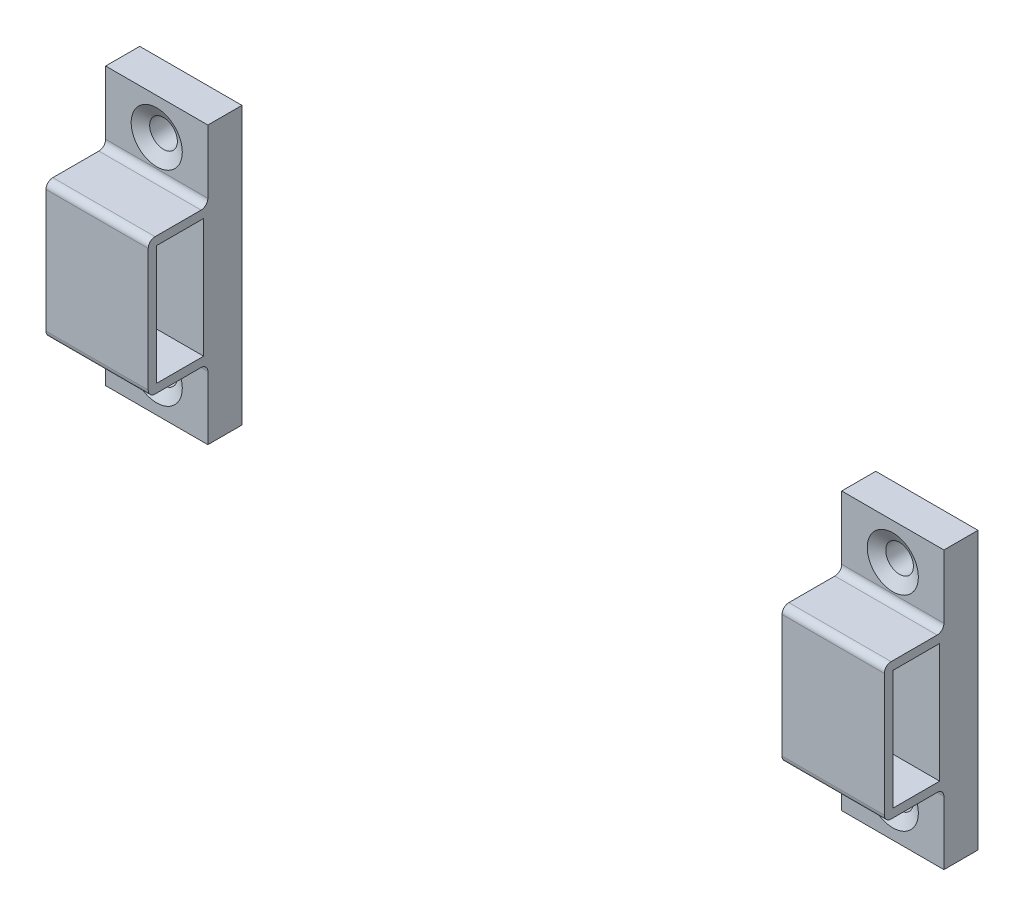
SolidWorks part; units mm, degrees
ref_plane "Front Plane" through (0, 0, 0) normal (0, 0, 1) x (1, 0, 0)
ref_plane "Top Plane" through (0, 0, 0) normal (0, 1, 0) x (1, 0, 0)
ref_plane "Right Plane" through (0, 0, 0) normal (1, 0, 0) x (0, 0, -1)
sketch "Sketch1" plane through (0, 0, 0) normal (0, 0, 1) x (1, 0, 0)
  line L0 (0, 25.7969) -> (0, -25.7969) construction
  line L1 (152.4, 0) -> (-152.4, 0) construction
  line L2 (9.525, 25.7969) -> (-9.525, 25.7969) construction
  line L3 (0, 19.05) -> (0, -19.05) construction
  line L4 (0, 9.525) -> (0, -9.525) construction
  line L5 (-152.4, 0) -> (-122.2375, 0) construction
  line L6 (152.4, 0) -> (127, 0) construction
  line L7 (152.4, 0) -> (-95.25, 0) construction
  line L8 (0, 12.7) -> (0, -12.7) construction
  line L9 (-4.1672, 0) -> (4.1672, 0) construction
  line L10 (0, 36.5125) -> (0, -36.5125) construction
sketch "Sketch3" plane through (0, 0, 0) normal (1, 0, 0) x (0, 0, -1)
  line L0 (3.175, 0) -> (-3.175, 0) construction
  line L1 (-9.525, 0) -> (9.525, 0) construction
  line L2 (-1.5875, 0) -> (1.5875, 0) construction
  line L3 (8.7312, 0) -> (-8.7312, 0) construction
sketch "Sketch4" plane through (0, 0, 0) normal (0, 0, 1) x (1, 0, 0)
  line L1 (-152.4, 9.525) -> (50.8, 9.525)
  line L2 (-152.4, 9.525) -> (-152.4, -9.525)
  line L3 (-152.4, -9.525) -> (50.8, -9.525)
  line L4 (50.8, 9.525) -> (50.8, -9.525)
  point P4 (152.4, 9.525)
  point P8 (-152.4, -9.525)
  dimension "D1" = 203.2
extrude "Boss-Extrude1" add sketch "Sketch4" along normal up to vertex (3.175 mm away) and the other way up to vertex (3.175 mm away) up to point (0, 0, 3.175) other way up to point (0, 0, -3.175)
chamfer "Chamfer1" distance 1.27 angle 45 4 edges at (50.8, -9.525, 0) (50.8, 0, -3.175) (50.8, 9.525, 0) (50.8, 0, 3.175)
sketch "Sketch5" plane through (0, 0, 3.175) normal (0, 0, 1) x (1, 0, 0)
  line L0 (-142.875, -7.9375) -> (-142.875, 0) construction
  line L5 (152.4, 0) -> (-152.4, 0) construction
  line L6 (-142.875, -7.9375) -> (-142.875, -9.525) construction
  line L7 (-152.4, -9.525) -> (49.53, -9.525) construction
  line L8 (-142.875, 0) -> (-142.875, 7.9375) construction
  line L9 (-142.875, 7.9375) -> (-142.875, 9.525) construction
  line L10 (49.53, 9.525) -> (-152.4, 9.525) construction
  line L12 (-152.4, -9.525) -> (-133.35, -9.525) construction
  line L13 (-152.4, -9.525) -> (-152.4, 9.525) construction
  line L14 (-152.4, 9.525) -> (-133.35, 9.525) construction
  line L15 (-133.35, -9.525) -> (-133.35, 9.525) construction
  line L16 (-152.4, -9.525) -> (-133.35, 9.525) construction
  line L17 (-152.4, 9.525) -> (-133.35, -9.525) construction
  line L18 (-152.4, 9.525) -> (-152.4, -9.525) construction
  line L19 (-95.25, 0) -> (-104.775, 0) construction
  line L20 (-142.875, 0) -> (-134.9375, 0) construction
  circle A0 centre (-142.875, 0) radius 7.9375
  dimension "D1" = 9.525
  dimension "D2" = 30.1625
extrude "Boss-Extrude2" add sketch "Sketch5" along normal blind 12.7
sketch "Sketch6" plane through (0, 0, 15.875) normal (0, 0, 1) x (1, 0, 0)
  line L0 (49.53, 9.525) -> (-152.4, 9.525) construction
  line L1 (-151.892, -9.525) -> (-133.858, -9.525)
  line L2 (-152.4, -9.017) -> (-152.4, 9.017)
  line L3 (-151.892, 9.525) -> (-133.858, 9.525)
  line L4 (-133.35, -9.017) -> (-133.35, 9.017)
  line L5 (-152.4, -9.525) -> (-133.35, 9.525) construction
  line L6 (-152.4, 9.525) -> (-133.35, -9.525) construction
  line L7 (-152.4, 9.525) -> (-152.4, -9.525) construction
  line L8 (-152.4, 9.017) -> (-151.892, 9.525)
  line L9 (-133.858, 9.525) -> (-133.35, 9.017)
  line L10 (-133.858, -9.525) -> (-133.35, -9.017)
  line L11 (-152.4, -9.017) -> (-151.892, -9.525)
  circle A0 centre (-142.875, 0) radius 7.9375 construction
  point P0 (-142.875, 0)
extrude "Boss-Extrude3" add sketch "Sketch6" along normal blind 3.175
chamfer "Chamfer2" distance 1.27 angle 45 4 edges at (-142.875, 9.525, 19.05) (-133.35, 0, 19.05) (-142.875, -9.525, 19.05) (-152.4, 0, 19.05)
fillet "Fillet1" radius 0.635 2 edges at (-134.9375, 0, 15.875) (-134.9375, 0, 3.175)
fillet "Fillet2" radius 0.254 8 edges at (-152.4, 0, 15.875) (-152.146, -9.271, 15.875) (-142.875, -9.525, 15.875) (-133.604, -9.271, 15.875) (-133.35, 0, 15.875) (-133.604, 9.271, 15.875) (-142.875, 9.525, 15.875) (-152.146, 9.271, 15.875)
ref_plane "Plane1" through (127, 0, 0) normal (1, 0, 0) x (0, 0, -1)
sketch "Sketch7" plane through (127, 0, 0) normal (1, 0, 0) x (0, 0, -1)
  line L0 (11.5094, 25.7969) -> (11.5094, -25.7969)
  line L1 (0, 0) -> (11.5094, 0) construction
  line L2 (11.5094, 25.7969) -> (5.1594, 25.7969)
  line L3 (5.1594, 25.7969) -> (5.1594, 12.7)
  line L4 (5.1594, 12.7) -> (-5.9531, 12.7)
  line L5 (-5.9531, 12.7) -> (-5.9531, -12.7)
  line L6 (-5.9531, -12.7) -> (5.1594, -12.7)
  line L7 (5.1594, -12.7) -> (5.1594, -25.7969)
  line L8 (5.1594, -25.7969) -> (11.5094, -25.7969)
  line L9 (0, 11.1125) -> (0, 12.7) construction
  line L10 (-4.3656, -11.1125) -> (4.3656, -11.1125)
  line L11 (-4.3656, -11.1125) -> (-4.3656, 11.1125)
  line L12 (-4.3656, 11.1125) -> (4.3656, 11.1125)
  line L13 (4.3656, -11.1125) -> (4.3656, 11.1125)
  line L14 (-4.3656, -11.1125) -> (4.3656, 11.1125) construction
  line L15 (-4.3656, 11.1125) -> (4.3656, -11.1125) construction
  line L16 (-4.3656, 0) -> (-5.9531, 0) construction
  line L17 (0, -11.1125) -> (0, -12.7) construction
  line L18 (0, 12.7) -> (0, -12.7) construction
  line L19 (-3.175, 9.525) -> (3.175, 9.525) construction
  point P21 (0, 0)
  dimension "D1" = 51.5938
  dimension "D2" = 17.4625
  dimension "D3" = 0.7937
  dimension "D4" = 1.5875
  dimension "D5" = 6.35
  dimension "D6" = 1.5875
extrude "Boss-Extrude4" add sketch "Sketch7" along normal mid plane 19.05 separate body
sketch "Sketch8" plane through (0, 0, -5.1594) normal (0, 0, 1) x (1, 0, 0)
  line L0 (127, 0) -> (127, 19.05) construction
  line L1 (127, 0) -> (127, -19.05) construction
  circle A0 centre (127, 19.05) radius 2.5797
  circle A1 centre (127, -19.05) radius 2.5797
  dimension "D2" = 5.1594
  dimension "D1" = 38.1
extrude "Cut-Extrude1" cut sketch "Sketch8" against normal through all
sketch "Sketch9" plane through (0, 0, -5.1594) normal (0, 0, 1) x (1, 0, 0)
  circle A0 centre (127, 19.05) radius 4.7625
  dimension "D1" = 9.525
extrude "Cut-Extrude2" cut sketch "Sketch9" against normal through all draft 60
sketch "Sketch10" plane through (0, 0, -5.1594) normal (0, 0, 1) x (1, 0, 0)
  circle A0 centre (127, -19.05) radius 4.7625
  circle A1 centre (127, 19.05) radius 4.7625 construction
extrude "Cut-Extrude3" cut sketch "Sketch10" against normal through all draft 60
fillet "Fillet4" radius 1.27 4 edges at (127, -12.7, -5.1594) (127, -12.7, 5.9531) (127, 12.7, 5.9531) (127, 12.7, -5.1594)
pattern_linear "阵列(线性)1" count 2 spacing 137.16 along (-1, 0, 0) of "Boss-Extrude4", "Cut-Extrude1", "Cut-Extrude2", "Cut-Extrude3"
delete or keep bodies "实体-删除/保留 1" type delete bodies bodies 106
equation "\"D1@Sketch7\"=\"Guide Height@Sketch1\""
equation "\"D2@Sketch7\"=\"Guide Depth@Sketch3\""
equation "\"D1@Boss-Extrude4\"=\"Guide Width@Sketch1\""
equation "\"D1@Sketch8\"=\"Mounting Hole Distance@Sketch1\""
equation "\"D3@LPattern1\"=\"Edge to Guide Mount 2@Sketch1\"-1"
equation "\"D2@Sketch11\"=\"Guide Width@Sketch1\""
equation "\"D1@Boss-Extrude5\"=\"Guide Height@Sketch1\""
equation "\"D2@Sketch5\"=\"Max Throw@Sketch1\""
equation "\"D1@Sketch16\"=\"Guide Width@Sketch1\""
equation "\"D2@Sketch16\"=\"Mortise Strike Plate Height@Sketch1\""
equation "\"D3@Sketch16\"=\"Mortise Strike Plate Hole Height@Sketch1\""
equation "\"D4@Sketch16\"=\"Mortise Strike Plate Hole Width@Sketch1\""
equation "\"D1@Boss-Extrude6\"=\"Mortise Strike Depth@Sketch3\""
equation "\"D2@Sketch17\"=13/64"
